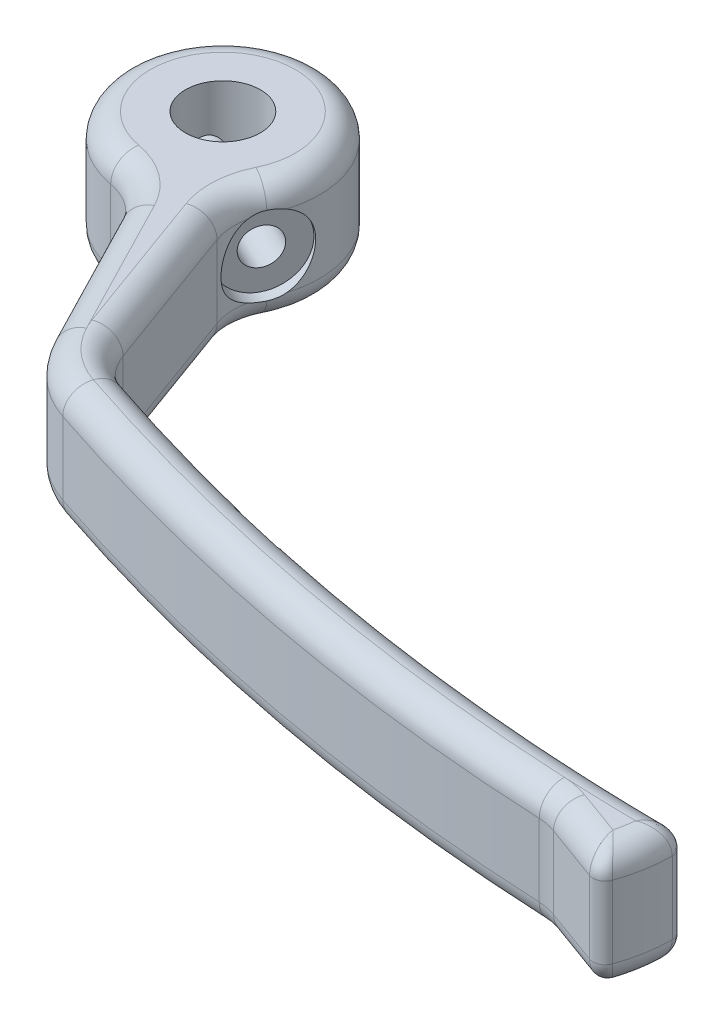
SolidWorks part; units mm, degrees
material "ABS"
ref_plane "Plan de face" through (0, 0, 0) normal (0, 0, 1) x (1, 0, 0)
ref_plane "Plan de dessus" through (0, 0, 0) normal (0, 1, 0) x (1, 0, 0)
ref_plane "Plan de droite" through (0, 0, 0) normal (1, 0, 0) x (0, 0, -1)
sketch "Esquisse1" plane through (0, 0, 0) normal (0, 1, 0) x (1, 0, 0)
  line L0 (70, -31.795) -> (70, -35.795)
  line L1 (6.1284, -5.1423) -> (11.4219, -19.6862)
  line L2 (0.8295, -7.9569) -> (8.1209, -22.1002)
  circle A0 centre (0, 0) radius 3.1
  arc A1 (6.1284, -5.1423) -> (0.8295, -7.9569) centre (0, 0) ccw
  arc A2 (13.2511, -26.5065) -> (70, -35.795) centre (70, 142.205) ccw
  arc A3 (14.5263, -22.7152) -> (70, -31.795) centre (70, 142.205) ccw
  circle A4 centre (0, 0) radius 15.5 construction
  arc A5 (13.2511, -26.5065) -> (8.1209, -22.1002) centre (16.1204, -17.9761) cw
  arc A6 (14.5263, -22.7152) -> (11.4219, -19.6862) centre (16.1204, -17.9761) cw
  circle A7 centre (0, 0) radius 80 construction
  dimension "D1" = 15.5
  dimension "D2" = 174
  dimension "D3" = 6.2
  dimension "D6" = 4
  dimension "D7" = 8
  dimension "D4" = 4
  dimension "D9" = 5
  dimension "D11" = 80
  dimension "D5" = 70
  dimension "D8" = 20
  dimension "D10" = 6
extrude "Boss.-Extru.1" add sketch "Esquisse1" along normal mid plane 10
fillet "Congé2" radius 1 2 edges at (70, 0, 35.795) (70, 0, 31.795)
sketch "Esquisse2" plane through (0, 5, 0) normal (0, 1, 0) x (1, 0, 0)
  line L0 (69.9397, -35.1342) -> (69.2557, -37.0136)
  line L1 (67.9739, -37.6113) -> (62.556, -35.6393)
  line L2 (62.556, -35.6393) -> (69.9397, -35.1342)
  line L3 (70, -34.7922) -> (70, -32.7922) construction
  arc A0 (68.9944, -35.7922) -> (70, -34.7922) centre (69, -34.7922) ccw construction
  arc A1 (69.2557, -37.0136) -> (67.9739, -37.6113) centre (68.316, -36.6716) cw
  arc A2 (13.2511, -26.5065) -> (68.9944, -35.7922) centre (70, 142.205) ccw construction
  dimension "D1" = 90
  dimension "D2" = 70
  dimension "D3" = 3
extrude "Boss.-Extru.2" add sketch "Esquisse2" against normal up to surface (10 mm away) up to face at (32.3952, -5, 23.0921)
fillet "Congé3" radius 5 3 edges at (6.1284, 0, 5.1423) (0.8295, 0, 7.9569) (62.556, 0, 35.6393)
sketch "Esquisse3" plane through (0, 5, 0) normal (0, 1, 0) x (1, 0, 0)
  line L0 (70, -32.7922) -> (70, -37.0136)
  line L1 (70, -37.0136) -> (69.2557, -37.0136)
  arc A0 (69.2557, -37.0136) -> (70, -32.7922) centre (57.6573, -32.7922) ccw
  arc A1 (70, -32.7922) -> (69.0057, -31.7922) centre (69, -32.7922) ccw construction
  arc A2 (67.9739, -37.6113) -> (69.2557, -37.0136) centre (68.316, -36.6716) ccw construction
extrude "Enlèv. mat.-Extru.1" cut sketch "Esquisse3" against normal through all
hole_wizard "Chambrage pour vis à tête cylindrique à 6 pans creux (ou vis CHC) M32" positions "Esquisse3D2" profile "Esquisse6" counterbore size "M3" standard "Ansi Metric" end condition through all
sketch3d "Esquisse3D2"
  line L0 (7.1789, 5, 3.5304) -> (7.1789, -5, 3.5304) construction
  point P6 (7.1789, 0, 3.5304)
sketch "Esquisse6" plane through (7.1789, 0, 3.5304) normal (0, 1, 0) x (0.4413, 0, -0.8974)
  line L0 (0, 0) -> (0, 18.7093)
  line L1 (0, 18.7093) -> (1.2, 18.7093)
  line L3 (1.2, 18.7093) -> (1.2, 1)
  line L4 (1.2, 1) -> (3.25, 1)
  line L5 (3.25, 1) -> (3.25, 0)
  line L7 (3.25, 0) -> (0, 0)
  line L11 (0, -6.35) -> (0, 107.95) construction
  dimension "Diamètre du perçage jusqu'au prochain" = 2.4
  dimension "Profondeur du perçage jusqu'au prochain" = 18.7093
  dimension "Diamètre du chambrage" = 6.5
  dimension "Profondeur du chambrage" = 1
sketch "Esquisse7" plane through (6.2815, 0, 3.0891) normal (0.8974, 0, 0.4413) x (0.4413, 0, -0.8974)
  circle A0 centre (0, 0) radius 1.5
  circle A1 centre (0, 0) radius 1.2 construction
  dimension "D1" = 3
extrude "Enlèv. mat.-Extru.2" cut sketch "Esquisse7" against normal blind 6
sketch "Esquisse8" plane through (6.2815, 0, 3.0891) normal (0.8974, 0, 0.4413) x (0.4413, 0, -0.8974)
  circle A0 centre (0, 0) radius 3.25
  circle A1 centre (0, 0) radius 3.25 construction
extrude "Enlèv. mat.-Extru.3" cut sketch "Esquisse8" along normal blind 6
fillet "Congé4" radius 2 28 edges at (69.7091, -5, 32.0871) (69.8125, -5, 34.9355) (68.7386, -5, 37.5779) (65.6261, -5, 36.7568) (62.5497, -5, 35.698) (37.2077, -5, 32.7484) (10.2564, -5, 24.8035) (5.1316, -5, 16.3018) (0.6697, -5, 8.7734) (-3.6079, -5, -7.1402) (6.673, -5, 5.4671) (9.1946, -5, 13.5666) (12.6286, -5, 21.5549) (10.2564, 5, 24.8035) (5.1316, 5, 16.3018) (0.6697, 5, 8.7734) (-3.6079, 5, -7.1402) (6.673, 5, 5.4671) (9.1946, 5, 13.5666) (12.6286, 5, 21.5549) (41.4036, 5, 29.4291) (69.7091, 5, 32.0871) (69.8125, 5, 34.9355) (68.7386, 5, 37.5779) (65.6261, 5, 36.7568) (62.5497, 5, 35.698) (41.4036, -5, 29.4291) (37.2077, 5, 32.7484)
